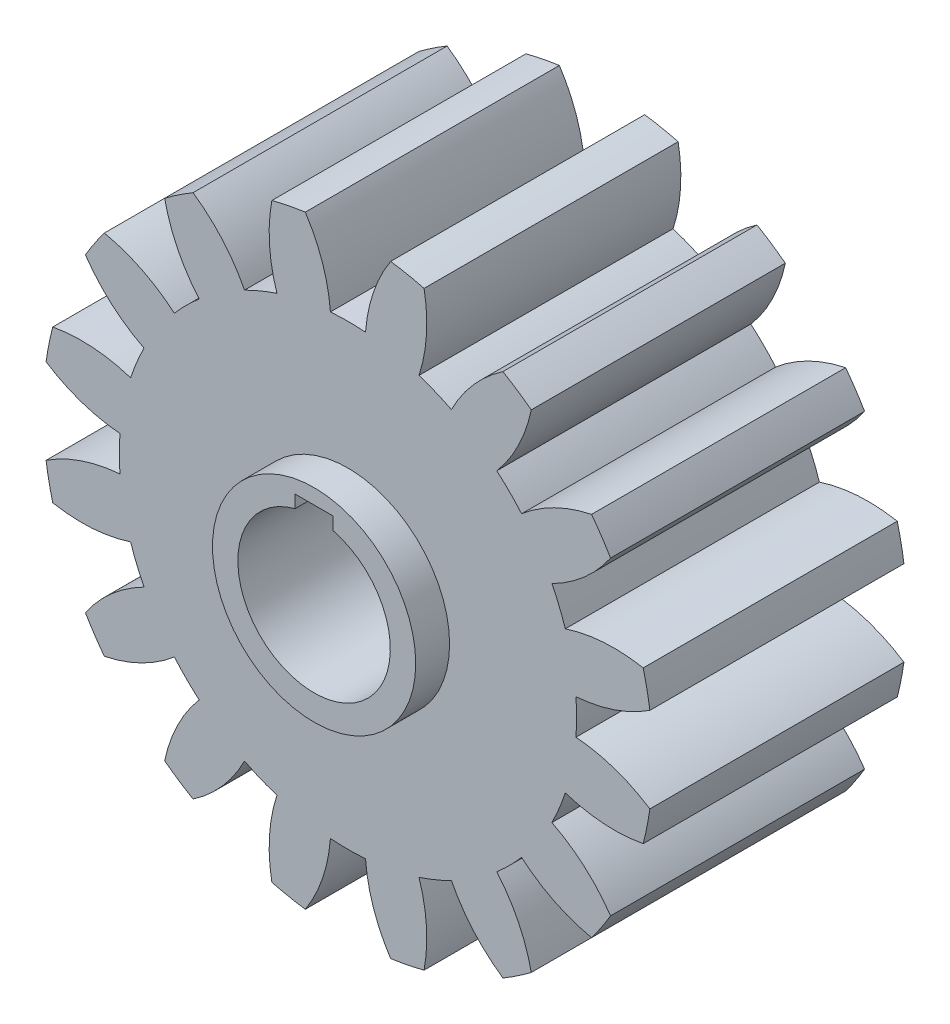
SolidWorks part; units mm, degrees
material "Plain Carbon Steel"
ref_plane "Front Plane" through (0, 0, 0) normal (0, 0, 1) x (1, 0, 0)
ref_plane "Top Plane" through (0, 0, 0) normal (0, 1, 0) x (1, 0, 0)
ref_plane "Right Plane" through (0, 0, 0) normal (1, 0, 0) x (0, 0, -1)
sketch "Sketch1" plane through (0, 0, 0) normal (0, 0, 1) x (1, 0, 0)
  circle A0 centre (0, 0) radius 16 construction
  circle A1 centre (0, 0) radius 18
  dimension "D1" = 32
  dimension "D2" = 36
extrude "Boss-Extrude1" add sketch "Sketch1" along normal mid plane 15
sketch "Sketch2" plane through (0, 0, 0) normal (0, 0, 1) x (1, 0, 0)
  line L0 (0, 18) -> (0, 0) construction
  line L1 (0, 0) -> (6.8883, 16.6298) construction
  line L2 (0, 0) -> (3.5116, 17.6541) construction
  line L3 (-1.0358, 13.4602) -> (0, 0) construction
  line L4 (-1.5683, 15.923) -> (1.5683, 15.923) construction
  line L5 (1.5683, 15.923) -> (4.6446, 15.311) construction
  line L6 (-2.2719, 17.8561) -> (0, 11.6142) construction
  circle A0 centre (0, 0) radius 18 construction
  circle A1 centre (0, 0) radius 14 construction
  circle A3 centre (0, 0) radius 18 construction
  arc A6 (-2.5185, 17.8229) -> (-1.0358, 13.4602) centre (-10.2915, 12.748) cw
  arc A7 (2.5185, 17.8229) -> (1.0358, 13.4602) centre (10.2915, 12.748) ccw
  circle A8 centre (0, 0) radius 16 construction
  arc A9 (1.0358, 13.4602) -> (-1.0358, 13.4602) centre (0, 0) ccw
  circle A10 centre (0, 0) radius 18
  arc A11 (2.5185, 17.8229) -> (-2.5185, 17.8229) centre (0, 0) ccw
  dimension "D1" = 22.5
  dimension "D4" = 20
  dimension "D3" = 0.5
  dimension "D5" = 0
extrude "Cut-Extrude1" cut sketch "Sketch2" against normal through all both and the other way through all
sketch "Sketch3" plane through (0, 0, 7.5) normal (0, 0, 1) x (1, 0, 0)
  line L1 (-1.125, 3.6071) -> (1.125, 3.6071)
  line L2 (-1.125, 3.6071) -> (-1.125, 5.1071)
  line L3 (-1.125, 5.1071) -> (1.125, 5.1071)
  line L4 (1.125, 3.6071) -> (1.125, 5.1071)
  circle A0 centre (0, 0) radius 6
  arc A1 (-1.125, 4.3571) -> (1.125, 4.3571) centre (0, 0) ccw
  point P8 (0, 3.6071)
  point P9 (-1.125, 4.3571)
  dimension "D1" = 12
  dimension "D2" = 9
  dimension "D3" = 2.25
  dimension "D4" = 1.5
extrude "Boss-Extrude2" add sketch "Sketch3" along normal blind 2 contours A0 A1 L2 L3 L4 region at (-5.8303, 0, 7.5)
extrude "Cut-Extrude2" cut sketch "Sketch3<3>" against normal through all both and the other way through all contours L2 A1 L4 L1 | L1 L4 L3 L2 region at (0, 4.3571, 7.5) region at (0, -0.1243, 7.5)
sketch "Sketch3<3>" plane through (0, 0, 7.5) normal (0, 0, 1) x (1, 0, 0) same geometry as "Sketch3"
pattern_circular "CirPattern1" count 16 over 360 about axis through (0, 0, 7.5) along (0, 0, 1) of "Cut-Extrude1"
equation "\"module\"= 2mm"
equation "\"pressure angle\"= 20"
equation "\"num of teeth\"= 16"
equation "\"D1@Sketch1\"= \"num of teeth\" * \"module\""
equation "\"D2@Sketch1\"= ( \"num of teeth\" + 2) * \"module\""
equation "\"D1@Sketch2\"= 360 / \"num of teeth\""
equation "\"D2@Sketch2\"= \"module\" * 2"
equation "\"D4@Sketch2\"= \"pressure angle\""
equation "\"D3@Sketch3\"= 9 / 4"
equation "\"D4@Sketch3\"= 9 / 6"
equation "\"D1@CirPattern1\"= \"num of teeth\""
